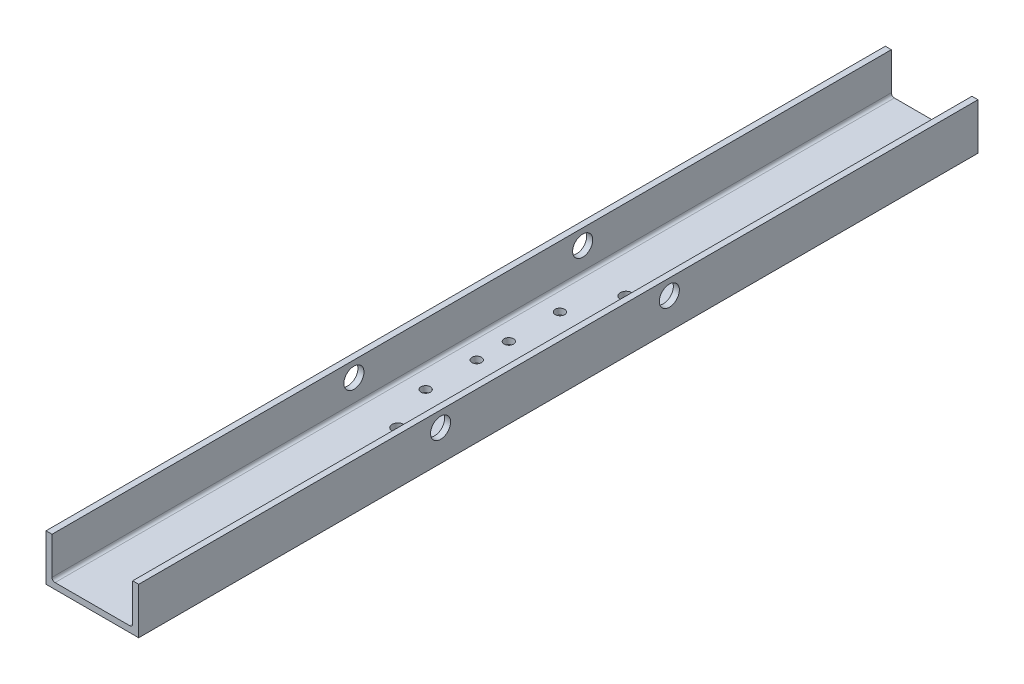
SolidWorks part; units mm, degrees
ref_plane "Front Plane" through (0, 0, 0) normal (0, 0, 1) x (1, 0, 0)
ref_plane "Top Plane" through (0, 0, 0) normal (0, 1, 0) x (1, 0, 0)
ref_plane "Right Plane" through (0, 0, 0) normal (1, 0, 0) x (0, 0, -1)
sketch "Sketch1" plane through (0, 0, 0) normal (0, 0, 1) x (1, 0, 0)
  line L0 (-25.4, 12.7) -> (-25.4, -12.7) construction
  line L1 (-25.4, -12.7) -> (25.4, -12.7) construction
  line L2 (25.4, -12.7) -> (25.4, 12.7) construction
  line L3 (22.098, -9.398) -> (-22.098, -9.398) construction
  line L4 (-22.098, -9.398) -> (-22.098, 12.7) construction
  line L6 (-22.098, 12.7) -> (-25.4, 12.7) construction
  line L7 (0, -12.7) -> (0, 0) construction
  line L8 (25.4, 12.7) -> (22.098, 12.7) construction
  line L9 (22.098, 12.7) -> (22.098, -9.398) construction
  line L10 (0, -9.398) -> (0, -12.7) construction
  point P4 (0, 0)
  point P11 (25.4, -9.398)
  dimension "Outside Height" = 25.4
  dimension "Outside Width" = 50.8
  dimension "Leg Thickness" = 3.302
  dimension "D1" = 12.7
  dimension "Inside Height" = 22.098
  dimension "Inside Width" = 44.196
  dimension "Base Thickness" = 3.302
sketch "Sketch2" plane through (0, 0, 0) normal (1, 0, 0) x (0, 0, -1)
  line L0 (230, 12.7) -> (-230, 12.7) construction
  line L1 (0, -9.398) -> (0, 12.7) construction
  point P0 (-179.2, 12.7)
  point P4 (0, 12.7)
  point P6 (179.2, 12.7)
  dimension "D1" = 50.8
  dimension "D2" = 50.8
  dimension "Length" = 460
sketch "Sketch3" plane through (0, 0, 0) normal (0, 0, 1) x (1, 0, 0)
  line L6 (-25.4, 12.7) -> (-25.4, -12.7)
  line L7 (-25.4, -12.7) -> (25.4, -12.7)
  line L8 (25.4, -12.7) -> (25.4, 12.7)
  line L9 (25.4, 12.7) -> (22.098, 12.7)
  line L10 (22.098, 12.7) -> (22.098, -9.398)
  line L11 (22.098, -9.398) -> (-22.098, -9.398)
  line L12 (-22.098, -9.398) -> (-22.098, 12.7)
  line L13 (-22.098, 12.7) -> (-25.4, 12.7)
extrude "Boss-Extrude1" add sketch "Sketch3" along normal mid plane 460
fillet "Fillet1" radius 1.651 2 edges at (22.098, -9.398, 0) (-22.098, -9.398, 0)
sketch "Sketch4" plane through (0, -9.398, 0) normal (0, 1, 0) x (1, 0, 0)
  line L0 (0, 230) -> (0, -230) construction
  line L1 (20.447, 230) -> (-20.447, 230) construction
  line L2 (20.447, -230) -> (-20.447, -230) construction
  line L3 (-23.5304, 0) -> (23.5304, 0) construction
  circle A0 centre (-10.5304, 8.79) radius 2.585
  circle A1 centre (10.4696, 8.79) radius 2.585
  circle A2 centre (-10.5304, 36.79) radius 2.585
  circle A3 centre (10.4696, 36.79) radius 2.585
  circle A4 centre (-10.5304, -36.79) radius 2.585
  circle A5 centre (10.4696, -36.79) radius 2.585
  circle A6 centre (10.4696, -8.79) radius 2.585
  circle A7 centre (-10.5304, -8.79) radius 2.585
  point P24 (0, 0)
  point P26 (0, 0)
  dimension "D1" = 5.17
  dimension "D2" = 5.17
  dimension "D3" = 28
  dimension "D4" = 8.79
  dimension "D5" = 8.79
  dimension "D6" = 28
extrude "Cut-Extrude1" cut sketch "Sketch4" against normal blind 10
sketch "Sketch5" plane through (0, -9.398, 0) normal (0, 1, 0) x (1, 0, 0)
  circle A0 centre (0, 62.5214) radius 3.18
  circle A2 centre (0, -62.52) radius 3.18
  circle A3 centre (-10.5304, -8.79) radius 2.585 construction
  dimension "D1" = 53.73
extrude "Cut-Extrude2" cut sketch "Sketch5" against normal through all
sketch "Sketch6" plane through (22.098, 0, 0) normal (-1, 0, 0) x (0, 0, 1)
  circle A0 centre (64.5436, 4.265) radius 5.5
  circle A1 centre (62.52, 14.351) radius 10.287 construction
  circle A2 centre (-60.8275, 4.2649) radius 5.5
  point P2 (-60.8275, 4.265)
  point P9 (0, 0)
  point P10 (-60.6004, 3.6963)
  dimension "D1" = 125.3711
extrude "Cut-Extrude3" cut sketch "Sketch6" against normal through all
sketch "Sketch7" plane through (-25.4, 0, 0) normal (-1, 0, 0) x (0, 0, 1)
  circle A0 centre (64.5436, 4.265) radius 5.5 construction
  circle A1 centre (-60.8275, 4.2649) radius 5.5 construction
  circle A2 centre (64.5436, 4.265) radius 5.5
  circle A3 centre (-60.8275, 4.2649) radius 5.5
extrude "Cut-Extrude4" cut sketch "Sketch7" against normal through all
equation "\"D1@Boss-Extrude1\"=\"Length@Sketch2\""
equation "\"D2@Sketch2\"=\"D1@Sketch2\""
equation "\"D1@Sketch1\"=\"Outside Height@Sketch1\"/2"
equation "\"D1@Fillet1\"=\"Leg Thickness@Sketch1\"*.5"
equation "\"D1@Sketch2\"=\"Outside Width@Sketch1\"*1"
